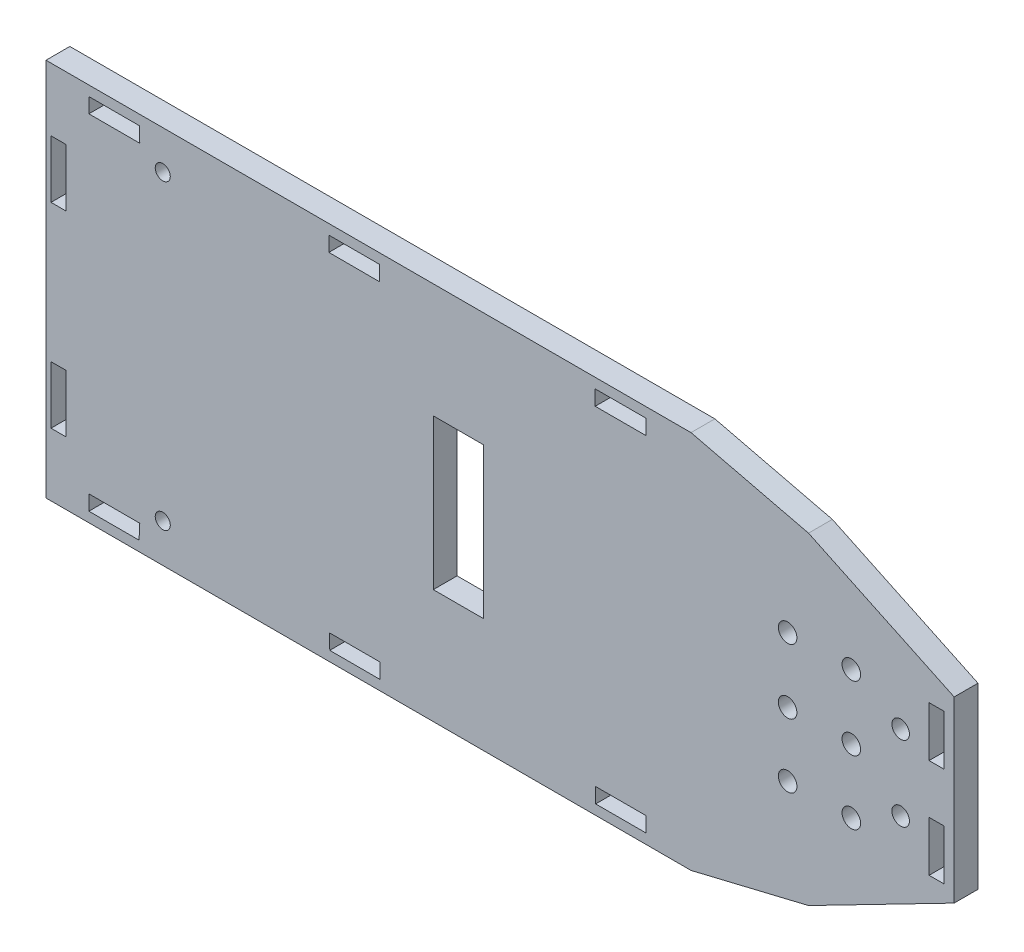
SolidWorks part; units mm, degrees
ref_plane "Front Plane" through (0, 0, 0) normal (0, 0, 1) x (1, 0, 0)
ref_plane "Top Plane" through (0, 0, 0) normal (0, 1, 0) x (1, 0, 0)
ref_plane "Right Plane" through (0, 0, 0) normal (1, 0, 0) x (0, 0, -1)
sketch "Sketch1" plane through (0, 0, 0) normal (0, 0, 1) x (1, 0, 0)
  line L1 (-90.5, -37.785) -> (90.5, -37.785)
  line L2 (-90.5, -37.785) -> (-90.5, 37.785)
  line L3 (-90.5, 37.785) -> (90.5, 37.785)
  line L4 (90.5, -37.785) -> (90.5, 37.785)
  line L5 (-90.5, -37.785) -> (90.5, 37.785) construction
  line L6 (-90.5, 37.785) -> (90.5, -37.785) construction
  point P0 (0, 0)
extrude "Boss-Extrude2" add sketch "Sketch1" along normal blind 4.75
sketch "Sketch6" plane through (0, 0, 4.75) normal (0, 0, 1) x (1, 0, 0)
  line L0 (-90.5, 0) -> (90.5, 0) construction
  line L1 (-90.5, 37.785) -> (-90.5, -37.785) construction
  line L2 (90.5, -37.785) -> (90.5, 37.785) construction
  line L3 (0, 37.785) -> (0, -37.785) construction
  line L4 (90.5, 37.785) -> (-90.5, 37.785) construction
  line L5 (-90.5, -37.785) -> (90.5, -37.785) construction
  line L10 (-17.18, 37.785) -> (-17.18, -37.785) construction
  line L11 (-81.9552, 32.802) -> (-71.8128, 32.7986)
  line L12 (-89.5, 25.2329) -> (-86.5, 25.2329)
  line L13 (-89.5, 25.2329) -> (-89.5, 13.75)
  line L14 (-89.5, 13.75) -> (-86.5, 13.75)
  line L15 (-86.5, 25.2329) -> (-86.5, 13.75)
  line L16 (-89.5, -13.75) -> (-86.5, -13.75)
  line L17 (-89.5, -13.75) -> (-89.5, -25.2329)
  line L18 (-89.5, -25.2329) -> (-86.5, -25.2329)
  line L19 (-86.5, -13.75) -> (-86.5, -25.2329)
  line L20 (-34.1308, 32.7983) -> (-34.1388, 35.785)
  line L21 (-34.1308, 32.7983) -> (-24.043, 32.7816)
  line L22 (-34.1388, 35.785) -> (-24.043, 35.785)
  line L23 (-24.043, 32.7816) -> (-24.043, 35.785)
  line L24 (-71.8128, 32.7986) -> (-71.8594, 35.785)
  line L25 (-81.9552, 32.802) -> (-81.9552, 35.785)
  line L26 (-81.9552, 35.785) -> (-71.8594, 35.785)
  line L27 (-81.9552, -32.785) -> (-71.8128, -32.7884)
  line L28 (-71.9552, -35.785) -> (-71.8128, -32.7884)
  line L29 (-81.9552, -35.785) -> (-71.9552, -35.785)
  line L30 (-81.9552, -35.785) -> (-81.9552, -32.785)
  line L31 (-33.9472, -35.801) -> (-23.9472, -35.8088)
  line L32 (-33.9472, -35.801) -> (-33.9552, -32.801)
  line L33 (-23.9472, -35.8088) -> (-23.9469, -32.8043)
  line L34 (-33.9552, -32.801) -> (-23.9469, -32.8043)
  line L35 (85.5, 14.9) -> (85.5, 4.9)
  line L36 (88.5, 14.9) -> (88.5, 4.9)
  line L37 (85.5, 4.9) -> (88.5, 4.9)
  line L38 (85.5, 14.9) -> (88.5, 14.9)
  line L39 (88.5, 9.9) -> (85.5, 9.9) construction
  line L40 (29.0528, 32.7816) -> (29.0528, 35.785)
  line L41 (18.957, 32.7816) -> (29.0528, 32.7816)
  line L42 (18.957, 32.7816) -> (18.957, 35.785)
  line L43 (18.957, 35.785) -> (29.0528, 35.785)
  line L44 (19.0531, -32.8054) -> (29.0528, -32.8063)
  line L45 (19.0528, -35.8054) -> (19.0531, -32.8054)
  line L46 (19.0528, -35.8054) -> (29.0528, -35.8063)
  line L47 (29.0528, -35.8063) -> (29.0528, -32.8063)
  line L50 (-67.23, -30.095) -> (79.8334, -30.095) construction
  line L51 (-13.3116, 15) -> (-3.3116, 15)
  line L52 (-13.3116, 15) -> (-13.3116, -15)
  line L53 (-13.3116, -15) -> (-3.3116, -15)
  line L54 (-3.3116, 15) -> (-3.3116, -15)
  line L59 (85.5, -14.9) -> (88.5, -14.9)
  line L64 (85.5, -4.9) -> (85.5, -14.9)
  line L65 (85.5, -4.9) -> (88.5, -4.9)
  line L66 (88.5, -4.9) -> (88.5, -14.9)
  line L67 (38.0552, -37.785) -> (61.4663, -32.14)
  line L68 (61.4663, -32.14) -> (90.5, -17.2)
  line L69 (38.0552, 37.785) -> (61.4663, 32.14)
  line L70 (61.4663, 32.14) -> (90.5, 18.3856)
  line L71 (79.8334, -30.095) -> (79.8334, -36.495)
  circle A2 centre (-67.23, 30.095) radius 1.5
  circle A3 centre (-67.23, -30.095) radius 1.5
  circle A12 centre (70.0065, -12.7534) radius 1.85
  circle A13 centre (70.0065, 12.8925) radius 1.85
  circle A14 centre (70.0065, 0) radius 1.85
  circle A15 centre (57.3065, 12.8925) radius 1.85
  circle A16 centre (57.3065, 0) radius 1.85
  circle A17 centre (57.3065, -12.7534) radius 1.85
  circle A20 centre (79.8334, -7.5) radius 1.75
  circle A21 centre (79.8334, 7.5) radius 1.75
  point P12 (0, 0)
  point P14 (0, 0)
  point P15 (0, 0)
  point P16 (0, 0)
  point P17 (0, 0)
  point P21 (90.5, 0)
  point P66 (0, 0)
  line M4 (90.5, -37.785) -> (90.5, 37.785)
  line M5 (90.5, 37.785) -> (-90.5, 37.785)
  line M7 (-90.5, -37.785) -> (90.5, -37.785)
  dimension "D1" = 43
  dimension "D3" = 27.5
  dimension "D2" = 43
  dimension "D4" = 15
  dimension "D6" = 2
  dimension "D5" = 7.5
  dimension "D7" = 2
  dimension "D8" = 2
  dimension "D9" = 2
  dimension "D10" = 1
  dimension "D11" = 13.75
extrude "Cut-Extrude7" cut sketch "Sketch6" against normal blind 9 contours L38 L35 L37 L36 | A14 | A12 | A17 | A16 | A15 | L43 L42 L41 L40 | L54 L51 L52 L53 | L46 L47 L44 L45 | L21 L23 L22 L20 | L26 L25 L11 L24 | A2 | L15 L12 L13 L14 | L19 L16 L17 L18 | L30 L29 L28 L27 | A3 | L34 L32 L31 L33 | L68 L67 M7 M4 | L69 L70 M4 M5 | A21 | L66 L65 L64 L59 | A20 | A13 | A21 | L59 L66 L65 L64 region at (-76.8947, 34.2915, 4.75) region at (-88, 19.4915, 4.75) region at (-88, -19.4915, 4.75) region at (-29.0842, 34.2877, 4.75) region at (-76.9204, -34.2823, 4.75) region at (-28.9479, -34.3036, 4.75) region at (87, 9.9, 4.75) region at (24.0049, 34.2833, 4.75) region at (24.0529, -34.3058, 4.75) region at (-8.3116, 0, 4.75) region at (87, -9.9, 4.75) region at (74.7992, 31.6648, 4.75) region at (75.0311, -31.3147, 4.75) region at (-67.23, 30.095, 4.75) region at (-67.23, -30.095, 4.75) region at (70.0065, -12.7534, 4.75) region at (70.0065, 12.8925, 4.75) region at (70.0065, 0, 4.75) region at (57.3065, 12.8925, 4.75) region at (57.3065, 0, 4.75) region at (57.3065, -12.7534, 4.75) region at (79.8334, -7.5, 4.75) region at (79.8334, 7.5, 4.75)
